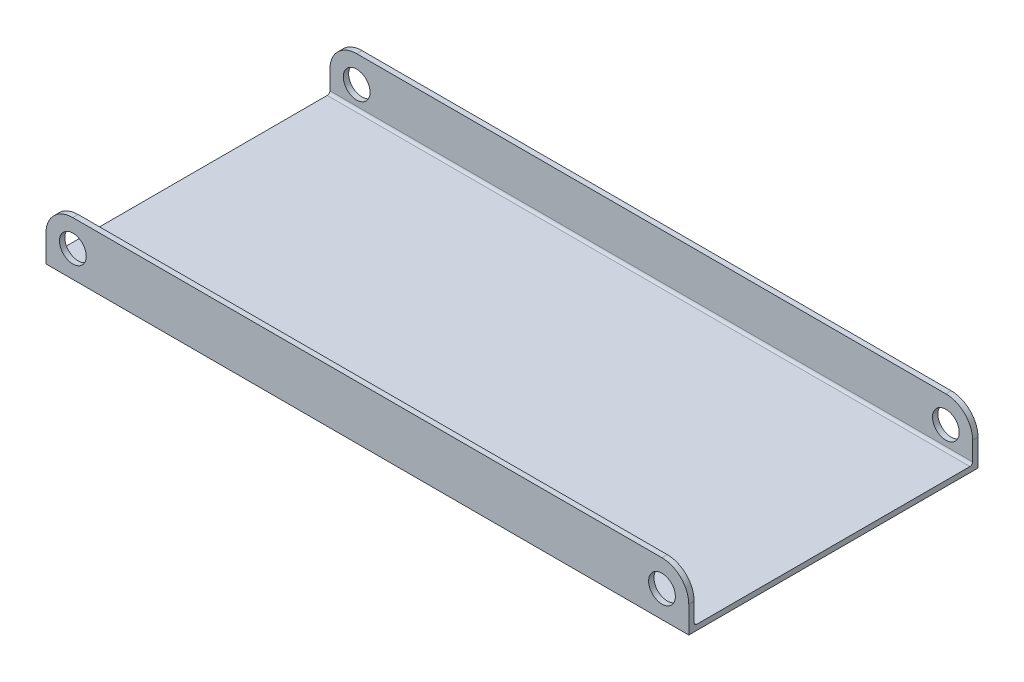
SolidWorks part; units mm, degrees
material "AISI 1020"
ref_plane "Front Plane" through (0, 0, 0) normal (0, 0, 1) x (1, 0, 0)
ref_plane "Top Plane" through (0, 0, 0) normal (0, 1, 0) x (1, 0, 0)
ref_plane "Right Plane" through (0, 0, 0) normal (1, 0, 0) x (0, 0, -1)
sketch "Sketch1" plane through (0, 0, 0) normal (0, 1, 0) x (1, 0, 0)
  line L0 (0, 34.29) -> (152.4, 34.29) construction
  line L1 (0, 0) -> (152.4, 0)
  line L2 (0, 0) -> (0, 68.58)
  line L3 (0, 68.58) -> (152.4, 68.58)
  line L4 (152.4, 0) -> (152.4, 68.58)
  line L5 (3.099, 0) -> (3.099, 1.27) construction
  line L6 (0, 1.27) -> (152.4, 1.27)
  line L7 (0, 68.58) -> (152.4, 68.58)
  line L8 (0, 67.31) -> (152.4, 67.31)
extrude "Boss-Extrude1" add sketch "Sketch1" along normal blind 12.7 contours L6 L2 L1 L4 region at (76.2, 0, -0.635)
extrude "Boss-Extrude2" add sketch "Sketch1<3>" along normal blind 1.27 contours L2 L6 L4 L3 region at (76.2, 0, -34.29)
sketch "Sketch1<3>" plane through (0, 0, 0) normal (0, 1, 0) x (1, 0, 0) same geometry as "Sketch1"
sketch "Sketch2" plane through (0, 0, 0) normal (0, 0, 1) x (1, 0, 0)
  line L0 (0, 6.35) -> (6.3736, 6.35) construction
  line L1 (0, 12.7) -> (0, 0) construction
  line L2 (152.4, 6.35) -> (146.05, 6.35) construction
  line L3 (152.4, 12.7) -> (152.4, 0) construction
  circle A0 centre (6.3736, 6.35) radius 3.175
  circle A1 centre (146.05, 6.35) radius 3.175
extrude "Cut-Extrude1" cut sketch "Sketch2" against normal blind 508
extrude "Boss-Extrude3" add sketch "Sketch1<5>" along normal blind 12.7 contours L2 L8 L4 L3 region at (76.2, 0, -67.945)
sketch "Sketch1<5>" plane through (0, 0, 0) normal (0, 1, 0) x (1, 0, 0) same geometry as "Sketch1"
sketch "Sketch3" plane through (0, 0, -68.58) normal (0, 0, -1) x (-1, 0, 0)
  line L0 (0, 6.35) -> (-6.35, 6.35) construction
  line L1 (0, 12.7) -> (0, 0) construction
  line L2 (-152.4, 6.35) -> (-146.05, 6.35) construction
  line L3 (-152.4, 12.7) -> (-152.4, 0) construction
  circle A0 centre (-6.35, 6.35) radius 3.175
  circle A1 centre (-146.05, 6.35) radius 3.175
extrude "Cut-Extrude2" cut sketch "Sketch3" against normal blind 12.7
fillet "Fillet1" radius 6.35 4 edges at (0, 12.7, -0.635) (152.4, 12.7, -0.635) (152.4, 12.7, -67.945) (0, 12.7, -67.945)
fillet "Fillet2" radius 0.635 2 edges at (76.2, 1.27, -1.27) (76.2, 1.27, -67.31)
equation "\"A\"= 20.5"
equation "\"B\"= 6.5"
equation "\"C\"= 36deg"
